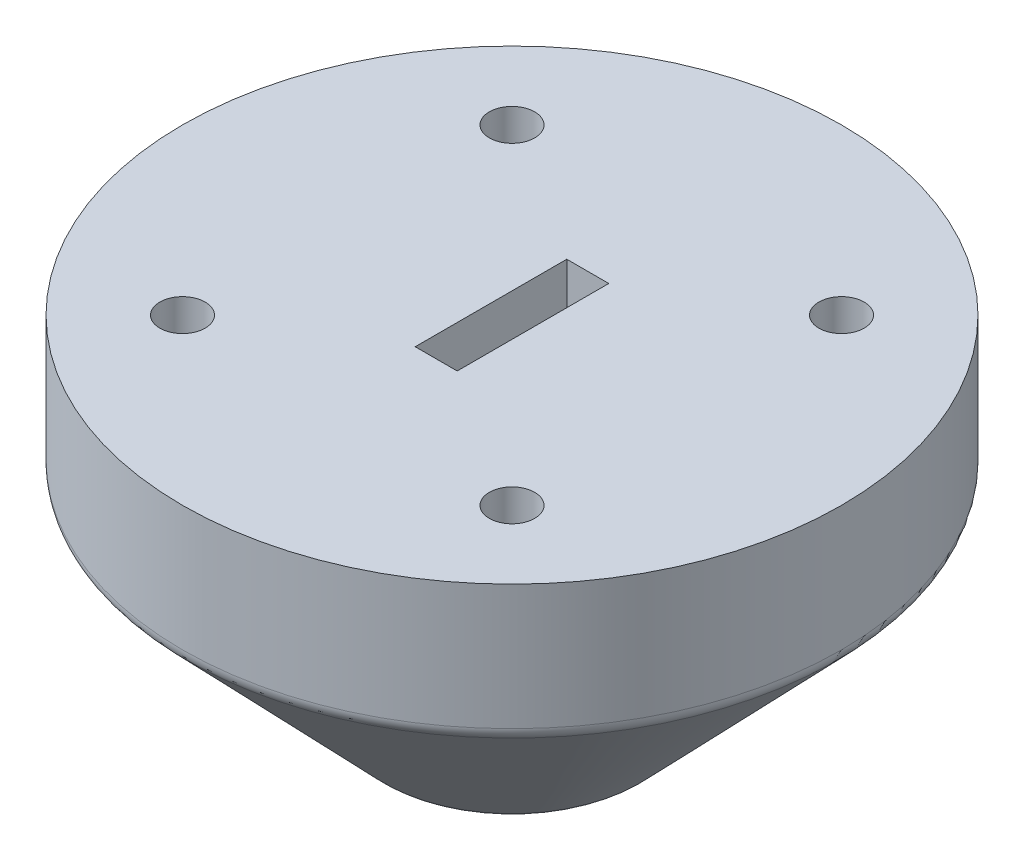
SolidWorks part; units mm, degrees
ref_plane "Front Plane" through (0, 0, 0) normal (0, 0, 1) x (1, 0, 0)
ref_plane "Top Plane" through (0, 0, 0) normal (0, 1, 0) x (1, 0, 0)
ref_plane "Right Plane" through (0, 0, 0) normal (1, 0, 0) x (0, 0, -1)
sketch "Sketch1" plane through (0, 0, 0) normal (0, 0, 1) x (1, 0, 0)
  line L0 (0, 0) -> (40, 0)
  line L1 (40, 0) -> (40, -16)
  line L2 (40, -16) -> (15, -42)
  line L3 (15, -42) -> (0, -42)
  line L4 (0, -42) -> (0, 0)
  dimension "D1" = 42
  dimension "D2" = 40
  dimension "D3" = 15
  dimension "D4" = 16
revolve "Revolve1" add sketch "Sketch1" angle 360 about L4
hole_wizard "Ø5.5mm Dowel Hole7" positions "Sketch9" profile "Sketch10" hole size "Ø5.0" standard "ISO"
sketch "Sketch9" plane through (0, 0, 0) normal (0, 1, 0) x (1, 0, 0)
  line L1 (-20, 20) -> (20, 20) construction
  line L2 (-20, 20) -> (-20, -20) construction
  line L3 (-20, -20) -> (20, -20) construction
  line L4 (20, 20) -> (20, -20) construction
  line L5 (-20, 20) -> (20, -20) construction
  line L6 (-20, -20) -> (20, 20) construction
  line L7 (0, 0) -> (0, -17.1882) construction
  line L8 (0, 0) -> (12.5207, 0) construction
  point P2 (20, -20)
  point P191 (-20, 20)
  point P192 (-20, -20)
  point P193 (20, 20)
  dimension "D1" = 40
  dimension "D2" = 40
sketch "Sketch10" plane through (20, 0, 20) normal (1, 0, 0) x (0, 0, 1)
  line L0 (0, 0) -> (0, 12.75)
  line L1 (0, 12.75) -> (2.75, 10)
  line L2 (2.75, 10) -> (2.75, 0)
  line L5 (2.75, 0) -> (0, 0)
  line L10 (0, 12.75) -> (-2.75, 10) construction
  line L11 (0, -6.35) -> (0, 107.95) construction
  dimension "Hole Dia." = 5.5
  dimension "Hole Depth" = 10
  dimension "Drill Angle" = 90
hole_wizard "Ø4.0mm Dowel Hole1" positions "Sketch15" profile "Sketch16" hole size "Ø4.0" standard "ISO"
sketch "Sketch15" plane through (0, 0, 0) normal (0, 1, 0) x (1, 0, 0)
  point P0 (-20, 20)
  point P3 (20, 20)
  point P6 (20, -20)
  point P9 (-20, -20)
  point P13 (0, 0)
sketch "Sketch16" plane through (-20, 0, -20) normal (1, 0, 0) x (0, 0, 1)
  line L0 (0, 0) -> (0, 22)
  line L1 (0, 22) -> (2, 20)
  line L2 (2, 20) -> (2, 0)
  line L5 (2, 0) -> (0, 0)
  line L10 (0, 22) -> (-2, 20) construction
  line L11 (0, -6.35) -> (0, 107.95) construction
  dimension "Hole Dia." = 4
  dimension "Hole Depth" = 20
  dimension "Drill Angle" = 90
sketch "Sketch13" plane through (0, 0, 0) normal (0, 0, 1) x (1, 0, 0)
  line L0 (0, 0) -> (0, -42) construction
  line L1 (-15, -42) -> (15, -42) construction
  line L2 (-2.55, 0) -> (2.55, 0)
  line L3 (40, 0) -> (-40, 0) construction
  line L4 (2.55, 0) -> (2.55, -20)
  line L5 (-2.55, 0) -> (-2.55, -20)
  line L6 (2.55, -20) -> (1, -40)
  line L7 (-2.55, -20) -> (-1, -40)
  line L8 (1, -40) -> (-1, -40)
  point P13 (0, -40)
  dimension "D1" = 20
  dimension "D2" = 5.1
  dimension "D3" = 2
  dimension "D4" = 20
extrude "Cut-Extrude1" cut sketch "Sketch13" against normal blind 9.2 and the other way blind 9.2
sketch "Sketch14" plane through (0, 0, 0) normal (1, 0, 0) x (0, 0, -1)
  line L0 (9.2, -40) -> (9.2, -20) construction
  line L1 (9.2, -30) -> (12.2, -27)
  line L2 (12.2, -27) -> (9.2, -24)
  line L3 (9.2, -24) -> (6.2, -27)
  line L4 (6.2, -27) -> (9.2, -30)
  line L5 (40, 0) -> (-40, 0) construction
  circle A0 centre (9.2, -27) radius 2.1213 construction
  dimension "D1" = 24
  dimension "D2" = 6
extrude "Boss-Extrude1" add sketch "Sketch14" along normal blind 10 and the other way blind 10
fillet "Fillet1" radius 2 1 edges at (0, -42, -15)
fillet "Fillet2" radius 2 1 edges at (0, -16, -40)
fillet "Fillet6" radius 1 1 edges at (1, -40, 0)
fillet "Fillet7" radius 1 1 edges at (-1, -40, 0)
fillet "Fillet8" radius 1 1 edges at (0, -27, -6.2)
